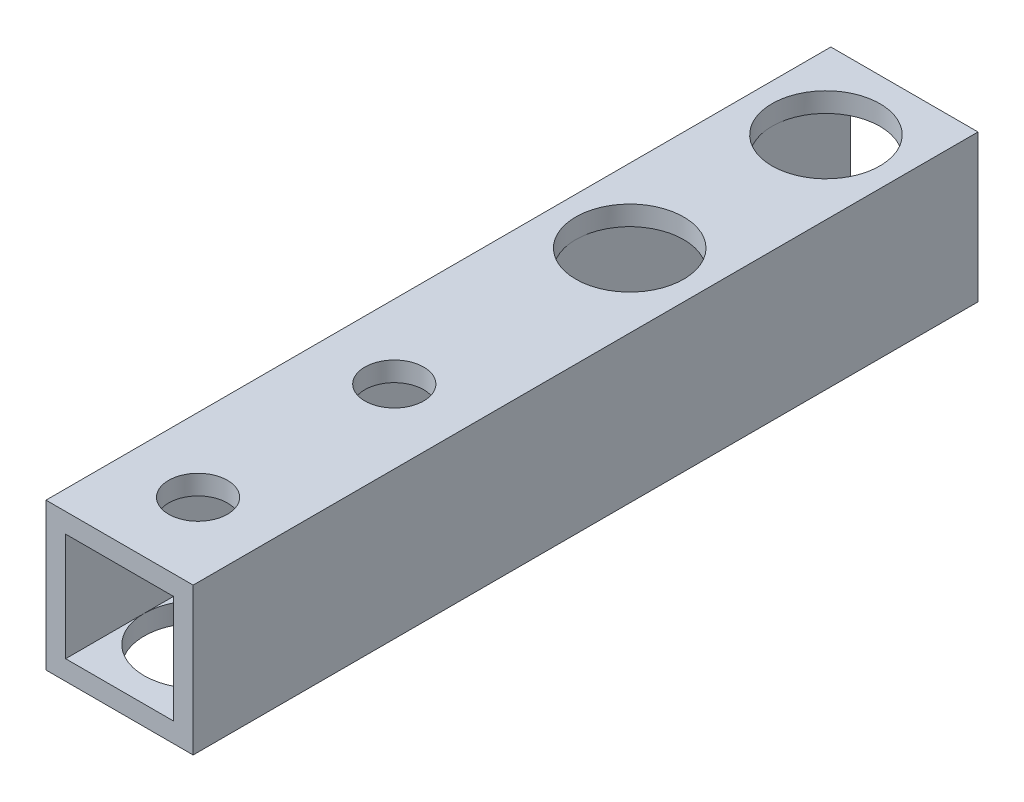
SolidWorks part; units mm, degrees
material "3.3535 (EN-AW 5754)"
ref_plane "Front" through (0, 0, 0) normal (0, 0, 1) x (1, 0, 0)
ref_plane "Top" through (0, 0, 0) normal (0, 1, 0) x (1, 0, 0)
ref_plane "Right" through (0, 0, 0) normal (1, 0, 0) x (0, 0, -1)
sketch "Esquisse1" plane through (0, 0, 0) normal (0, 0, 1) x (1, 0, 0)
  line L0 (2.75, -2.75) -> (2.75, 2.75)
  line L1 (-3.75, -3.75) -> (3.75, -3.75)
  line L2 (-3.75, -3.75) -> (-3.75, 3.75)
  line L3 (-3.75, 3.75) -> (3.75, 3.75)
  line L4 (3.75, -3.75) -> (3.75, 3.75)
  line L5 (-3.75, -3.75) -> (3.75, 3.75) construction
  line L6 (-3.75, 3.75) -> (3.75, -3.75) construction
  line L7 (-2.75, 2.75) -> (2.75, 2.75)
  line L8 (-2.75, -2.75) -> (-2.75, 2.75)
  line L9 (-2.75, -2.75) -> (2.75, -2.75)
  point P0 (0, 0)
  dimension "D1" = 1
  dimension "D2" = 7.5
extrude "Boss.-Extru.1" add sketch "Esquisse1" along normal blind 40
sketch "Esquisse2" plane through (0, 3.75, 0) normal (0, 1, 0) x (1, 0, 0)
  line L0 (-3.75, -20) -> (3.75, -20) construction
  line L1 (-3.75, -40) -> (-3.75, 0) construction
  line L2 (3.75, -40) -> (3.75, 0) construction
  line L3 (3.75, 0) -> (-3.75, 0) construction
  circle A0 centre (0, -4) radius 1.5
  circle A1 centre (0, -14) radius 1.5
  circle A2 centre (0, -26) radius 1.5
  circle A3 centre (0, -36) radius 1.5
  dimension "D1" = 4
  dimension "D2" = 10
  dimension "D3" = 3
  dimension "D4" = 12
extrude "Enlèv. mat.-Extru.1" cut sketch "Esquisse2" against normal through all
sketch "Esquisse3" plane through (0, 3.75, 0) normal (0, 1, 0) x (1, 0, 0)
  circle A0 centre (0, -4) radius 2.75
  circle A1 centre (0, -14) radius 2.75
  dimension "D1" = 5.5
extrude "Enlèv. mat.-Extru.2" cut sketch "Esquisse3" against normal blind 2
sketch "Esquisse4" plane through (0, -3.75, 0) normal (0, -1, 0) x (1, 0, 0)
  circle A0 centre (0, 26) radius 2.75
  circle A1 centre (0, 36) radius 2.75
  circle A2 centre (0, 4) radius 2.75 construction
extrude "Enlèv. mat.-Extru.3" cut sketch "Esquisse4" against normal blind 2
